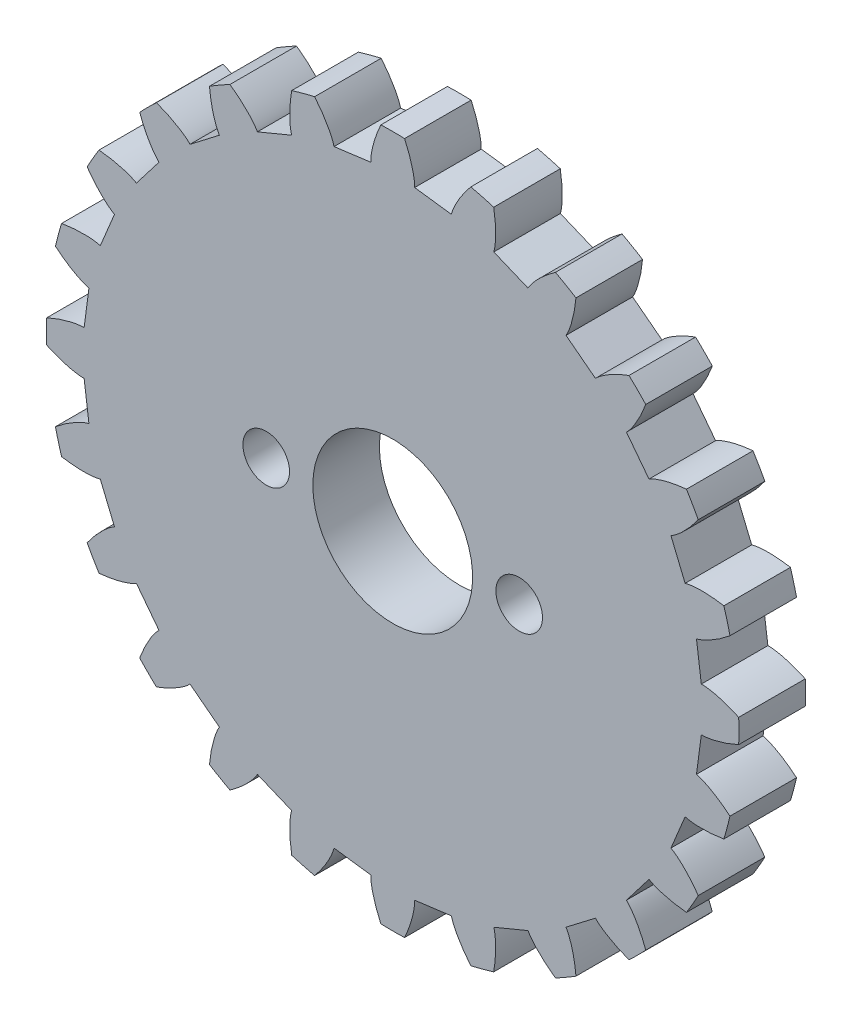
SolidWorks part; units mm, degrees
material "Plain Carbon Steel"
ref_plane "Front Plane" through (0, 0, 0) normal (0, 0, 1) x (1, 0, 0)
ref_plane "Top Plane" through (0, 0, 0) normal (0, 1, 0) x (1, 0, 0)
ref_plane "Right Plane" through (0, 0, 0) normal (1, 0, 0) x (0, 0, -1)
sketch "Sketch1" plane through (0, 0, 0) normal (0, 1, 0) x (1, 0, 0)
  line L0 (0, 0) -> (26, 0)
  line L1 (26, 0) -> (26, -5)
  line L2 (26, -5) -> (0, -5)
  line L3 (0, -5) -> (0, 0)
  line L4 (0, -1) -> (0, -4) construction
  dimension "D1" = 26
  dimension "D2" = 5
revolve "Revolve1" add sketch "Sketch1" angle 360 about L4
sketch "Sketch2" plane through (0, 0, 0) normal (0, 0, 1) x (1, 0, 0)
  spline S0 degree 4 poles (23.177, 1.6482) (23.1813, 1.6485) (23.1935, 1.6491) (23.2164, 1.6496) (23.254, 1.6497) (23.3019, 1.6487) (23.3639, 1.646) (23.437, 1.6411) (23.5174, 1.6339) (23.6049, 1.6241) (23.6923, 1.6126) (23.7796, 1.5995) (23.8665, 1.585) (23.9718, 1.5657) (24.0981, 1.5401) (24.2458, 1.5067) (24.4133, 1.4648) (24.5839, 1.4176) (24.7518, 1.3675) (24.9214, 1.3128) (25.0854, 1.2568) (25.2557, 1.1944) (25.4128, 1.1347) (25.5887, 1.063) (25.7306, 1.0037) (25.9177, 0.9206) (26.028, 0.8699) (26.1572, 0.8089) (26.2145, 0.7809) (26.2497, 0.7637) knots 0 0 0 0 0 0.005377 0.015084 0.028532 0.04661 0.064855 0.092111 0.119476 0.146842 0.174209 0.201575 0.228941 0.256307 0.307035 0.361767 0.4165 0.471232 0.525964 0.580697 0.635429 0.690161 0.744894 0.799626 0.854358 0.909091 0.954545 1 1 1 1 1 construction
  spline S1 degree 4 poles (23.177, 1.6482) (23.1813, 1.6485) (23.1935, 1.6491) (23.2164, 1.6496) (23.254, 1.6497) (23.3019, 1.6487) (23.3639, 1.646) (23.437, 1.6411) (23.5174, 1.6339) (23.6049, 1.6241) (23.6923, 1.6126) (23.7796, 1.5995) (23.8665, 1.585) (23.9718, 1.5657) (24.0981, 1.5401) (24.2458, 1.5067) (24.4133, 1.4648) (24.5839, 1.4176) (24.7518, 1.3675) (24.9214, 1.3128) (25.0854, 1.2568) (25.2557, 1.1944) (25.4128, 1.1347) (25.5887, 1.063) (25.7306, 1.0037) (25.8771, 0.9386) (25.9484, 0.9063) (25.9848, 0.8896) knots 0 0 0 0 0 0.005377 0.015084 0.028532 0.04661 0.064855 0.092111 0.119476 0.146842 0.174209 0.201575 0.228941 0.256307 0.307035 0.361767 0.4165 0.471232 0.525964 0.580697 0.635429 0.690161 0.744894 0.799626 0.854358 0.909091 0.909091 0.909091 0.909091 0.909091
  spline S2 degree 4 poles (22.8139, 4.4066) (22.8181, 4.4075) (22.83, 4.41) (22.8523, 4.4154) (22.8886, 4.4251) (22.9346, 4.4385) (22.9938, 4.4571) (23.0631, 4.4807) (23.1389, 4.5085) (23.221, 4.5406) (23.3024, 4.5744) (23.3833, 4.6096) (23.4635, 4.6461) (23.5602, 4.692) (23.6756, 4.7494) (23.8096, 4.8199) (23.9605, 4.9038) (24.1131, 4.9935) (24.2624, 5.0853) (24.412, 5.1821) (24.556, 5.2786) (24.7043, 5.3829) (24.8406, 5.4813) (24.9919, 5.5961) (25.1137, 5.69) (25.2728, 5.8188) (25.3663, 5.8963) (25.4752, 5.9886) (25.5233, 6.0305) (25.553, 6.0563) knots 0 0 0 0 0 0.005377 0.015084 0.028532 0.04661 0.064855 0.092111 0.119476 0.146842 0.174209 0.201575 0.228941 0.256307 0.307035 0.361767 0.4165 0.471232 0.525964 0.580697 0.635429 0.690161 0.744894 0.799626 0.854358 0.909091 0.954545 1 1 1 1 1 construction
  spline S3 degree 4 poles (22.8139, 4.4066) (22.8181, 4.4075) (22.83, 4.41) (22.8523, 4.4154) (22.8886, 4.4251) (22.9346, 4.4385) (22.9938, 4.4571) (23.0631, 4.4807) (23.1389, 4.5085) (23.221, 4.5406) (23.3024, 4.5744) (23.3833, 4.6096) (23.4635, 4.6461) (23.5602, 4.692) (23.6756, 4.7494) (23.8096, 4.8199) (23.9605, 4.9038) (24.1131, 4.9935) (24.2624, 5.0853) (24.412, 5.1821) (24.556, 5.2786) (24.7043, 5.3829) (24.8406, 5.4813) (24.9919, 5.5961) (25.1137, 5.69) (25.2383, 5.7909) (25.2988, 5.8405) (25.3296, 5.8661) knots 0 0 0 0 0 0.005377 0.015084 0.028532 0.04661 0.064855 0.092111 0.119476 0.146842 0.174209 0.201575 0.228941 0.256307 0.307035 0.361767 0.4165 0.471232 0.525964 0.580697 0.635429 0.690161 0.744894 0.799626 0.854358 0.909091 0.909091 0.909091 0.909091 0.909091
  spline S4 degree 4 poles (22.7775, 4.6829) (22.7807, 4.6587) (22.7869, 4.6115) (22.7943, 4.5548) (22.8117, 4.4234) (22.8198, 4.3613) (22.8431, 4.1843) (22.8567, 4.0812) (22.8772, 3.9253) (22.894, 3.798) (22.9128, 3.6552) (22.9298, 3.5256) (22.9476, 3.3909) (22.9638, 3.2678) (22.9809, 3.1377) (22.9981, 3.0069) (23.0161, 2.8701) (23.0345, 2.7307) (23.0532, 2.5884) (23.0711, 2.4528) (23.0907, 2.3041) (23.1075, 2.1759) (23.1295, 2.009) (23.1444, 1.8957) (23.1712, 1.6924) (23.1801, 1.6248) (23.1989, 1.4819) (23.2062, 1.4268) (23.211, 1.39) (23.2135, 1.371) knots 0 0 0 0 0 0.028849 0.052878 0.083333 0.124324 0.163161 0.206806 0.246995 0.288912 0.331781 0.370109 0.409255 0.448242 0.482806 0.525716 0.568843 0.611704 0.653696 0.694186 0.738248 0.782176 0.823818 0.871169 0.916667 0.958584 0.979292 1 1 1 1 1 construction
  spline S5 degree 4 poles (22.8139, 4.4066) (22.8176, 4.3783) (22.8244, 4.3263) (22.8431, 4.1843) (22.8567, 4.0812) (22.8772, 3.9253) (22.894, 3.798) (22.9128, 3.6552) (22.9298, 3.5256) (22.9476, 3.3909) (22.9638, 3.2678) (22.9809, 3.1377) (22.9981, 3.0069) (23.0161, 2.8701) (23.0345, 2.7307) (23.0532, 2.5884) (23.0711, 2.4528) (23.0907, 2.3041) (23.1075, 2.1759) (23.1295, 2.009) (23.1444, 1.8957) (23.1648, 1.7407) (23.1729, 1.6796) (23.177, 1.6482) knots 0.083333 0.083333 0.083333 0.083333 0.083333 0.124324 0.163161 0.206806 0.246995 0.288912 0.331781 0.370109 0.409255 0.448242 0.482806 0.525716 0.568843 0.611704 0.653696 0.694186 0.738248 0.782176 0.823818 0.871169 0.916667 0.916667 0.916667 0.916667 0.916667
  spline S6 degree 4 poles (22.5838, 0.7731) (23.0672, 0.7897) (23.6703, 0.8103) (25.5078, 0.8732) (26.4501, 0.9055) (28.7534, 0.9843) (30.1565, 1.0324) (32.1757, 1.1015) (33.8803, 1.1599) (35.8485, 1.2272) (37.6947, 1.2904) (39.6506, 1.3574) (41.5311, 1.4218) (43.4321, 1.4869) (45.2708, 1.5498) (47.0129, 1.6094) (48.7163, 1.6678) (50.2285, 1.7195) (51.6384, 1.7678) (52.9613, 1.8131) (54.2605, 1.8576) (55.4506, 1.8983) (56.8677, 1.9468) (57.8956, 1.982) (59.7111, 2.0441) (60.37, 2.0667) (62.0621, 2.1246) (62.6297, 2.1441) (63.1349, 2.1614) (63.3918, 2.1702) knots 0 0 0 0 0 0.041667 0.083333 0.123541 0.166753 0.209392 0.256181 0.300395 0.346612 0.394832 0.44205 0.489269 0.53291 0.580271 0.622911 0.660113 0.699653 0.729462 0.759701 0.79242 0.822588 0.854043 0.885331 0.916667 0.957078 0.978539 1 1 1 1 1 construction
  spline S7 degree 4 poles (25.9848, 0.8896) (26.3263, 0.9013) (27.0223, 0.9251) (28.7534, 0.9843) (30.1565, 1.0324) (32.1757, 1.1015) (33.8803, 1.1599) (35.8485, 1.2272) (37.6947, 1.2904) (39.6506, 1.3574) (41.5311, 1.4218) (43.4321, 1.4869) (45.2708, 1.5498) (47.0129, 1.6094) (48.7163, 1.6678) (50.2285, 1.7195) (51.6384, 1.7678) (52.9613, 1.8131) (54.2605, 1.8576) (55.4506, 1.8983) (56.8677, 1.9468) (57.8956, 1.982) (59.1656, 2.0255) (59.6986, 2.0437) (59.9648, 2.0528) knots 0.083333 0.083333 0.083333 0.083333 0.083333 0.123541 0.166753 0.209392 0.256181 0.300395 0.346612 0.394832 0.44205 0.489269 0.53291 0.580271 0.622911 0.660113 0.699653 0.729462 0.759701 0.79242 0.822588 0.854043 0.885331 0.916667 0.916667 0.916667 0.916667 0.916667
  spline S8 degree 4 poles (59.9935, 0.8853) (59.9921, 0.9686) (59.9891, 1.1296) (59.9859, 1.3474) (59.9691, 1.9373) (59.9603, 2.1956) (59.9292, 2.9561) (59.9042, 3.3875) (59.8676, 4.0111) (59.8299, 4.5186) (59.7847, 5.0956) (59.7358, 5.63) (59.6811, 6.1892) (59.6218, 6.733) (59.5573, 7.2845) (59.4875, 7.8317) (59.4133, 8.3783) (59.3328, 8.9276) (59.2494, 9.4683) (59.1575, 10.0226) (59.0664, 10.5515) (58.9607, 11.1205) (58.8658, 11.6204) (58.7398, 12.2323) (58.6522, 12.6554) (58.4855, 13.3981) (58.4271, 13.6498) (58.2906, 14.224) (58.2374, 14.4352) (58.1986, 14.5915) (58.1784, 14.6723) knots 0 0 0 0 0 0.020959 0.041918 0.083333 0.123016 0.162698 0.202381 0.242063 0.281746 0.321429 0.361111 0.400794 0.440476 0.480159 0.519841 0.559524 0.599206 0.638889 0.678571 0.718254 0.757937 0.797619 0.837302 0.876984 0.916667 0.958082 0.979041 1 1 1 1 1 construction
  spline S9 degree 4 poles (59.9648, 2.0528) (59.9608, 2.1679) (59.9523, 2.3919) (59.9292, 2.9561) (59.9042, 3.3875) (59.8676, 4.0111) (59.8299, 4.5186) (59.7847, 5.0956) (59.7358, 5.63) (59.6811, 6.1892) (59.6218, 6.733) (59.5573, 7.2845) (59.4875, 7.8317) (59.4133, 8.3783) (59.3328, 8.9276) (59.2494, 9.4683) (59.1575, 10.0226) (59.0664, 10.5515) (58.9607, 11.1205) (58.8658, 11.6204) (58.7398, 12.2323) (58.6522, 12.6554) (58.5285, 13.2064) (58.4788, 13.425) (58.4528, 13.5371) knots 0.083333 0.083333 0.083333 0.083333 0.083333 0.123016 0.162698 0.202381 0.242063 0.281746 0.321429 0.361111 0.400794 0.440476 0.480159 0.519841 0.559524 0.599206 0.638889 0.678571 0.718254 0.757937 0.797619 0.837302 0.876984 0.916667 0.916667 0.916667 0.916667 0.916667
  spline S10 degree 4 poles (61.7739, 14.3063) (61.7039, 14.2901) (61.5796, 14.2613) (61.4666, 14.2351) (60.8505, 14.0924) (60.4206, 13.9929) (58.8446, 13.6279) (58.2932, 13.5002) (56.7254, 13.1371) (55.8234, 12.9282) (54.568, 12.6374) (53.4429, 12.3769) (52.0511, 12.0546) (50.5992, 11.7183) (49.0504, 11.3596) (47.4563, 10.9905) (45.8632, 10.6215) (44.3102, 10.2618) (42.7618, 9.9032) (41.1907, 9.5394) (39.6063, 9.1725) (38.0428, 8.8104) (36.385, 8.4264) (34.8232, 8.0647) (33.0593, 7.6562) (31.5267, 7.3013) (29.6304, 6.8621) (28.2966, 6.5532) (25.8856, 5.9949) (25.0823, 5.8088) (23.5273, 5.4487) (22.7343, 5.2651) (22.3407, 5.1739) (22.1153, 5.1217) (22.0166, 5.0988) knots 0 0 0 0 0 0.005334 0.010668 0.021335 0.042671 0.083333 0.112698 0.136843 0.163043 0.191355 0.228657 0.25743 0.298405 0.34029 0.382676 0.419052 0.457933 0.497208 0.537818 0.578079 0.616034 0.656645 0.70114 0.741113 0.784 0.826386 0.866769 0.916667 0.958333 0.979167 0.989583 1 1 1 1 1 construction
  spline S11 degree 4 poles (58.4528, 13.5371) (58.2096, 13.4808) (57.7636, 13.3775) (56.7254, 13.1371) (55.8234, 12.9282) (54.568, 12.6374) (53.4429, 12.3769) (52.0511, 12.0546) (50.5992, 11.7183) (49.0504, 11.3596) (47.4563, 10.9905) (45.8632, 10.6215) (44.3102, 10.2618) (42.7618, 9.9032) (41.1907, 9.5394) (39.6063, 9.1725) (38.0428, 8.8104) (36.385, 8.4264) (34.8232, 8.0647) (33.0593, 7.6562) (31.5267, 7.3013) (29.6304, 6.8621) (28.2966, 6.5532) (26.4619, 6.1283) (25.7428, 5.9618) (25.3296, 5.8661) knots 0.083333 0.083333 0.083333 0.083333 0.083333 0.112698 0.136843 0.163043 0.191355 0.228657 0.25743 0.298405 0.34029 0.382676 0.419052 0.457933 0.497208 0.537818 0.578079 0.616034 0.656645 0.70114 0.741113 0.784 0.826386 0.866769 0.916667 0.916667 0.916667 0.916667 0.916667
extrude "Cut-Extrude2" cut sketch "Sketch2" against normal blind 6 and the other way blind 6
ref_axis "Axis1" through (0, 0, -0.25) along (0, 0, 1)
pattern_circular "CirPattern1" count 24 over 360 about axis through (0, 0, -0.25) along (0, 0, 1) of "Cut-Extrude2"
sketch "Sketch3" plane through (0, 0, 0) normal (0, 0, 1) x (1, 0, 0)
  circle A0 centre (0, 0) radius 6
  circle A1 centre (9.5, 0) radius 1.75
  circle A2 centre (-9.5, 0) radius 1.75
  dimension "D1" = 12
  dimension "D3" = 3.5
  dimension "D5" = 3.5
  dimension "D2" = 9.5
  dimension "D4" = 9.5
extrude "Cut-Extrude4" cut sketch "Sketch3" against normal blind 7 and the other way blind 7
equation "\"TrigProbe\"= cos(60)"
equation "\"SqrProbe\"= sqr(2)"
equation "\"AtnProbe\"= atn(1)"
equation "\"ToothCount\" = 24"
equation "\"DP\"= 12.7"
equation "\"PA\"= 14.5"
equation "\"PArad\"= \"PA\" * 3.14159265358979 / 180"
equation "\"Rb\"= \"ToothCount\" / \"DP\" * cos(\"PA\") / 2"
equation "\"Ra\"= (\"ToothCount\" + 2) / \"DP\" / 2"
equation "\"Tmax\"= sqr(\"Ra\" * \"Ra\" / (\"Rb\" * \"Rb\") - 1)"
equation "\"Delta\"= 3.14159265358979 / (2 * \"ToothCount\") + tan(\"PA\") - \"PArad\""
equation "\"Gamma\"= 2 * 3.14159265358979 / \"ToothCount\""
equation "\"ThetaL\"= atn(\"Tmax\") * 3.14159265358979 / 180 - \"Tmax\" + \"Delta\""
equation "\"ThetaU\"= \"Tmax\" - atn(\"Tmax\") * 3.14159265358979 / 180 - \"Delta\" + \"Gamma\""
equation "\"D1@Sketch1\" = \"Ra\""
equation "\"D1@CirPattern1\" = \"ToothCount\""
